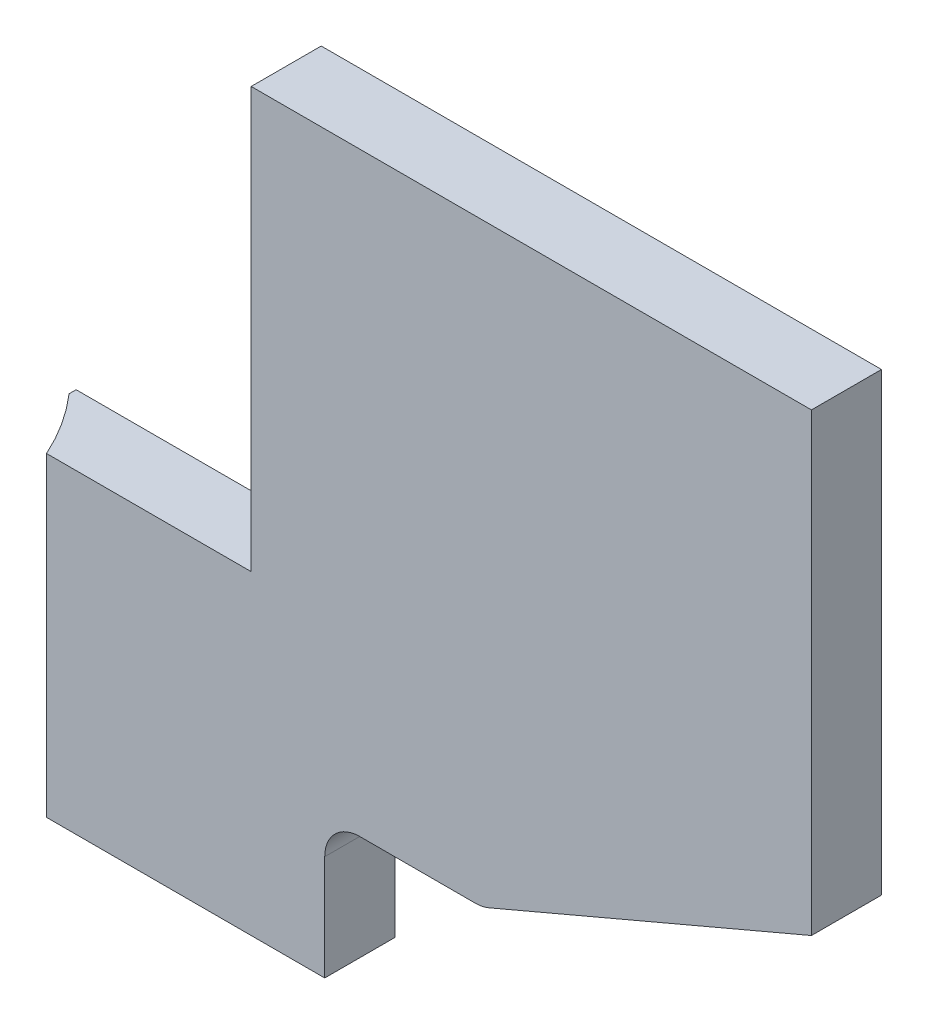
SolidWorks part; units mm, degrees
ref_plane "Front Plane" through (0, 0, 0) normal (0, 0, 1) x (1, 0, 0)
ref_plane "Top Plane" through (0, 0, 0) normal (0, 1, 0) x (1, 0, 0)
ref_plane "Right Plane" through (0, 0, 0) normal (1, 0, 0) x (0, 0, -1)
sketch "Sketch1" plane through (0, 0, 0) normal (0, 0, 1) x (1, 0, 0)
  line L0 (0, -55) -> (0, 55) construction
  line L1 (-40, -32.5) -> (40, -32.5)
  line L2 (-40, -32.5) -> (-40, 32.5)
  line L3 (-40, 32.5) -> (40, 32.5)
  line L4 (40, -32.5) -> (40, 32.5)
  line L5 (-40, -32.5) -> (40, 32.5) construction
  line L6 (-40, 32.5) -> (40, -32.5) construction
  point P0 (0, 0)
  point P23 (0, 0)
  dimension "D1" = 80
  dimension "D2" = 65
extrude "Boss-Extrude1" add sketch "Sketch1" along normal blind 10 contours L1 L4 L3 L2
sketch "Sketch3" plane through (0, -32.5, 0) normal (0, -1, 0) x (1, 0, 0)
  line L1 (-40, 10) -> (40, 10)
  line L2 (-40, 10) -> (-40, 0)
  line L3 (-40, 0) -> (40, 0)
  line L4 (40, 10) -> (40, 0)
extrude "Boss-Extrude2" add sketch "Sketch3" along normal blind 40
sketch "Sketch4" plane through (-40, 0, 0) normal (-1, 0, 0) x (0, 0, 1)
  line L0 (10, -72.5) -> (10, 32.5) construction
  line L1 (0, -72.5) -> (10, -72.5)
  line L2 (0, -72.5) -> (0, -27.5)
  line L3 (0, -27.5) -> (10, -27.5)
  line L4 (10, -72.5) -> (10, -27.5)
  dimension "D1" = 45
extrude "Boss-Extrude3" add sketch "Sketch4" along normal blind 35
sketch "Sketch5" plane through (0, -27.5, 0) normal (0, 1, 0) x (1, 0, 0)
  line L1 (-40, 0) -> (40, 0) construction
  line L5 (-75, -10) -> (-75, 0) construction
  circle A0 centre (-102.5, -25) radius 36.5
  dimension "D1" = 73
  dimension "D2" = 25
  dimension "D3" = 27.5
extrude "Cut-Extrude2" cut sketch "Sketch5" against normal through all
sketch "Sketch6" plane through (0, 0, 10) normal (0, 0, 1) x (1, 0, 0)
  line L0 (40, -72.5) -> (-69.2246, -72.5) construction
  line L1 (-29.5, -72.5) -> (40, -72.5)
  line L2 (-29.5, -72.5) -> (-29.5, -57.5)
  line L3 (-24.5, -52.5) -> (-8.0196, -52.5)
  line L6 (-6.0618, -52.1008) -> (40, -32.5)
  line L7 (40, -72.5) -> (40, 32.5) construction
  line L9 (40, -32.5) -> (40, -72.5)
  arc A0 (-29.5, -57.5) -> (-24.5, -52.5) centre (-24.5, -57.5) cw
  arc A1 (-8.0196, -52.5) -> (-6.0618, -52.1008) centre (-8.0196, -47.5) ccw
  point P13 (-29.5, -52.5)
  point P16 (-7, -52.5)
  dimension "D5" = 5
  dimension "D1" = 20
  dimension "D2" = 22.5
  dimension "D3" = 40
  dimension "D4" = 69.5
extrude "Cut-Extrude3" cut sketch "Sketch6" against normal through all
